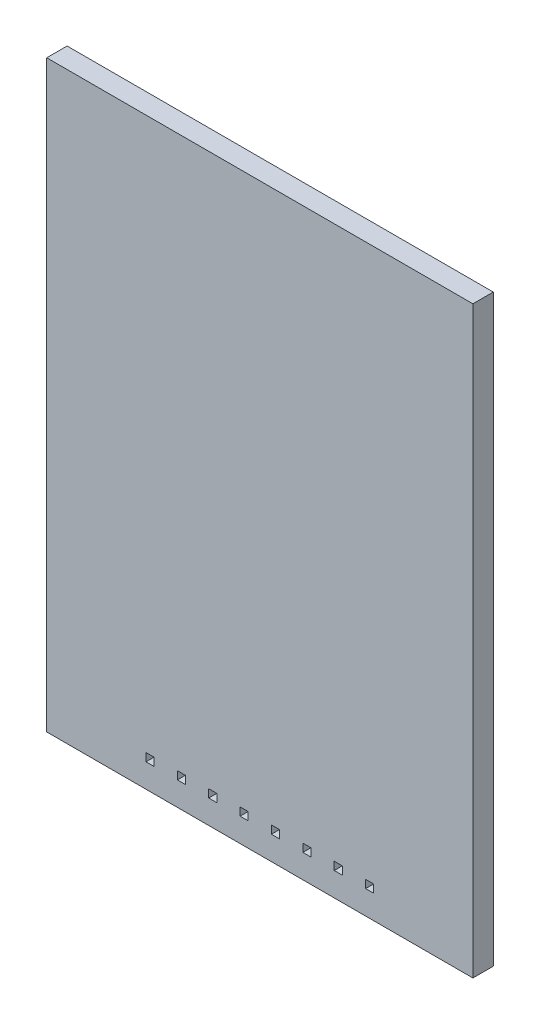
SolidWorks part; units mm, degrees
note: The reader was unsure of these and kept them because the rebuilt part matched: shared geometry of "Sketch2<2>".
ref_plane "Front Plane" through (0, 0, 0) normal (0, 0, 1) x (1, 0, 0)
ref_plane "Top Plane" through (0, 0, 0) normal (0, 1, 0) x (1, 0, 0)
ref_plane "Right Plane" through (0, 0, 0) normal (1, 0, 0) x (0, 0, -1)
sketch "Sketch1" plane through (0, 0, 0) normal (0, 0, 1) x (1, 0, 0)
  line L1 (17.25, -23.635) -> (-17.25, -23.635)
  line L2 (17.25, -23.635) -> (17.25, 23.635)
  line L3 (17.25, 23.635) -> (-17.25, 23.635)
  line L4 (-17.25, -23.635) -> (-17.25, 23.635)
  line L5 (17.25, -23.635) -> (-17.25, 23.635) construction
  line L6 (17.25, 23.635) -> (-17.25, -23.635) construction
  point P0 (0, 0)
  dimension "D1" = 34.5
  dimension "D2" = 47.27
extrude "Boss-Extrude1" add sketch "Sketch1" along normal blind 1.65
sketch "Sketch2" plane through (0, 0, 0) normal (0, 0, -1) x (-1, 0, 0)
  line L0 (0, 0) -> (0, -23.635) construction
  line L1 (17.25, -23.635) -> (-17.25, -23.635) construction
  line L3 (-1.595, -21.06) -> (-0.945, -21.06)
  line L4 (-1.595, -21.06) -> (-1.595, -21.71)
  line L5 (-1.595, -21.71) -> (-0.945, -21.71)
  line L6 (-0.945, -21.06) -> (-0.945, -21.71)
  line L7 (-1.595, -21.06) -> (-0.945, -21.71) construction
  line L8 (-1.595, -21.71) -> (-0.945, -21.06) construction
  point P5 (-1.27, -21.385)
  dimension "D1" = 0.65
  dimension "D2" = 2.25
  dimension "D3" = 2.54
extrude "Boss-Extrude2" add sketch "Sketch2" along normal blind 8.5 and the other way offset from surface (3.05 mm away) 1.4 other way up to face at (0, 0, 1.65)
extrude "Cut-Extrude1" cut sketch "Sketch2<2>" against normal through all both and the other way through all
sketch "Sketch2<2>" plane through (0, 0, 0) normal (0, 0, -1) x (-1, 0, 0) same geometry as "Sketch2"
pattern_linear "LPattern1" count 4 spacing 2.54 along (1, 0, 0) of "Cut-Extrude1"
mirror "Mirror1" about plane through (0, 0, 0) normal (1, 0, 0) of "Boss-Extrude2", "LPattern1"
sketch "Sketch3" plane through (0, 0, 0) normal (0, 0, 1) x (1, 0, 0)
  line L1 (0, 0) -> (0, -25.8877) construction
  line L2 (-17.25, -23.635) -> (17.25, -23.635) construction
  circle A0 centre (-15, -18.135) radius 1.2
  circle A1 centre (15, -18.135) radius 1.2
  dimension "D1" = 2.4
  dimension "D2" = 30
  dimension "D3" = 5.5
extrude "Cut-Extrude2" [suppressed] cut sketch "Sketch3" along normal through all
equation "\"screen_pcb_width\" = 34.5mm"
equation "\"D1@Sketch1\"=\"screen_pcb_width\""
